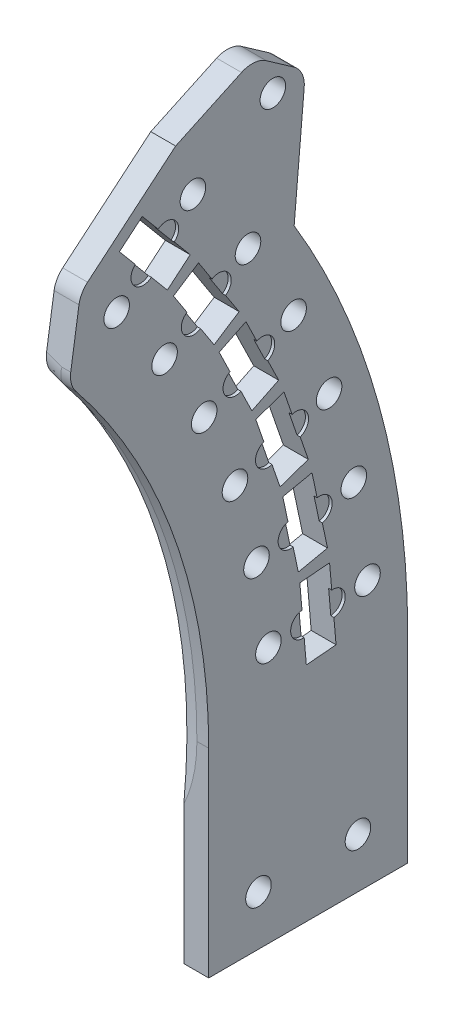
SolidWorks part; units mm, degrees
material "6061-T6 (SS)"
ref_plane "Front Plane" through (0, 0, 0) normal (0, 0, 1) x (1, 0, 0)
ref_plane "Top Plane" through (0, 0, 0) normal (0, 1, 0) x (1, 0, 0)
ref_plane "Right Plane" through (0, 0, 0) normal (1, 0, 0) x (0, 0, -1)
sketch "Sketch1" plane through (0, 0, 0) normal (1, 0, 0) x (0, 0, -1)
  line L0 (0, 0) -> (152.4, 0) construction
  line L1 (0, 0) -> (116.7452, 97.9608) construction
  line L2 (152.4, 0) -> (152.4, -50.8)
  line L3 (152.4, -50.8) -> (203.2, -50.8)
  line L4 (203.2, -50.8) -> (203.2, 0)
  line L5 (116.7452, 97.9608) -> (155.6602, 130.6144) construction
  line L6 (152.4, 0) -> (203.2, 0) construction
  line L7 (116.7452, 97.9608) -> (155.6602, 130.6144) construction
  line L9 (0, 0) -> (0, 168.3639) construction
  line L28 (152.4, -50.8) -> (152.4, -38.1) construction
  line L29 (152.4, -38.1) -> (203.2, -38.1) construction
  line L30 (0, 0) -> (136.2027, 114.2876) construction
  line L33 (155.6602, 130.6144) -> (143.9558, 137.372)
  line L34 (143.9558, 137.372) -> (119.6339, 116.9635)
  line L35 (119.6339, 116.9635) -> (116.7452, 97.9608)
  arc A0 (152.4, 0) -> (116.7452, 97.9608) centre (0, 0) ccw
  arc A1 (203.2, 0) -> (155.6602, 130.6144) centre (0, 0) ccw
  circle A32 centre (165.1, -38.1) radius 3.2639
  circle A33 centre (190.5, -38.1) radius 3.2639
  point P11 (151.8201, 13.2825)
  point P24 (150.0847, 26.464)
  dimension "D24" = 6.5278
  dimension "D25" = 6.5278
  dimension "D1" = 152.4
  dimension "D2" = 40
  dimension "D3" = 50.8
  dimension "D4" = 50.8
  dimension "D10" = 90
  dimension "D21" = 12.7
  dimension "D22" = 12.7
  dimension "D23" = 12.7
  dimension "D28" = 12.7
  dimension "D29" = 31.75
  dimension "D30" = 110
extrude "Boss-Extrude1" add sketch "Sketch1" along normal blind 6.35
sketch "Sketch2" plane through (0, 0, 0) normal (0, 1, 0) x (1, 0, 0)
  line L0 (0, 0) -> (-25.4, 0) construction
  line L1 (-25.4, 0) -> (-25.4, 38.1) construction
  line L2 (-25.4, 38.1) -> (-143.256, 38.1)
  line L3 (-143.256, 38.1) -> (92.456, 38.1)
  line L4 (0, 0) -> (-60.886, 0) construction
  arc A0 (92.456, 38.1) -> (-143.256, 38.1) centre (-25.4, 38.1) ccw
  dimension "D3" = 235.712
  dimension "D1" = 25.4
  dimension "D2" = 38.1
revolve "Cut-Revolve2" cut sketch "Sketch2" angle 360 about L4 region at (-25.4, 0, -88.1196)
sketch "Sketch5" plane through (0, 0, 0) normal (0, 0, 1) x (1, 0, 0)
  line L0 (-1000, 0) -> (49000, 0) construction
fillet "Fillet1" radius 6.35 4 edges at (4.8412, 97.9608, -116.7452) (3.175, 116.9635, -119.6339) (3.175, 130.6144, -155.6602)
sketch "Sketch6" plane through (6.35, 0, 0) normal (1, 0, 0) x (0, 0, -1)
  line L0 (0, 0) -> (177.8, 0) construction
  line L1 (0, 0) -> (136.2027, 114.2876) construction
  line L2 (0, 0) -> (192.938, 16.8799) construction
  line L3 (0, 0) -> (189.4427, 40.2673) construction
  line L4 (0, 0) -> (183.1233, 63.0544) construction
  line L5 (0, 0) -> (174.0739, 84.9015) construction
  line L6 (0, 0) -> (162.4295, 105.483) construction
  line L7 (0, 0) -> (148.3637, 124.4919) construction
  line L8 (0, 0) -> (167.6347, 14.6661) construction
  line L9 (0, 0) -> (164.5978, 34.9863) construction
  line L10 (175.6607, 24.9297) -> (177.321, 5.9522)
  line L11 (183.2517, 25.5938) -> (184.912, 6.6163)
  line L12 (175.6607, 24.9297) -> (183.2517, 25.5938)
  line L13 (184.912, 6.6163) -> (177.321, 5.9522)
  line L14 (182.7274, 29.1021) -> (175.2739, 27.5178)
  line L15 (171.3132, 46.1515) -> (175.2739, 27.5178)
  line L16 (171.3132, 46.1515) -> (178.7666, 47.7358)
  line L17 (178.7666, 47.7358) -> (182.7274, 29.1021)
  line L18 (177.8187, 51.154) -> (170.6138, 48.6732)
  line L19 (164.4118, 66.6853) -> (170.6138, 48.6732)
  line L20 (164.4118, 66.6853) -> (171.6166, 69.1662)
  line L21 (171.6166, 69.1662) -> (177.8187, 51.154)
  line L22 (170.2591, 72.4434) -> (163.4103, 69.103)
  line L23 (155.0594, 86.225) -> (163.4103, 69.103)
  line L24 (155.0594, 86.225) -> (161.9082, 89.5654)
  line L25 (161.9082, 89.5654) -> (170.2591, 72.4434)
  line L26 (160.1614, 92.6528) -> (153.7708, 88.5026)
  line L27 (143.3954, 104.4793) -> (153.7708, 88.5026)
  line L28 (143.3954, 104.4793) -> (149.7861, 108.6295)
  line L29 (149.7861, 108.6295) -> (160.1614, 92.6528)
  line L30 (147.6761, 111.4809) -> (141.8388, 106.5829)
  line L31 (129.5937, 121.176) -> (141.8388, 106.5829)
  line L32 (129.5937, 121.176) -> (135.431, 126.0741)
  line L33 (135.431, 126.0741) -> (147.6761, 111.4809)
  arc A0 (177.8, 0) -> (136.2027, 114.2876) centre (0, 0) ccw construction
  arc A1 (184.15, 0) -> (141.0671, 118.3693) centre (0, 0) ccw construction
  circle A2 centre (192.938, 16.8799) radius 9.525 construction
  arc A3 (203.2, 0) -> (156.395, 129.7338) centre (0, 0) ccw construction
  circle A4 centre (167.6347, 14.6661) radius 9.525 construction
  circle A5 centre (167.6347, 14.6661) radius 3.2639
  circle A6 centre (192.938, 16.8799) radius 3.2639
  circle A7 centre (164.5978, 34.9863) radius 3.2639
  circle A8 centre (164.5978, 34.9863) radius 9.525 construction
  circle A9 centre (189.4427, 40.2673) radius 3.2639
  circle A10 centre (189.4427, 40.2673) radius 9.525 construction
  circle A11 centre (159.1071, 54.785) radius 3.2639
  circle A12 centre (159.1071, 54.785) radius 9.525 construction
  circle A13 centre (183.1233, 63.0544) radius 3.2639
  circle A14 centre (183.1233, 63.0544) radius 9.525 construction
  circle A15 centre (151.2446, 73.7669) radius 3.2639
  circle A16 centre (151.2446, 73.7669) radius 9.525 construction
  circle A17 centre (174.0739, 84.9015) radius 3.2639
  circle A18 centre (174.0739, 84.9015) radius 9.525 construction
  circle A19 centre (141.1273, 91.6491) radius 3.2639
  circle A20 centre (141.1273, 91.6491) radius 9.525 construction
  circle A21 centre (162.4295, 105.483) radius 3.2639
  circle A22 centre (162.4295, 105.483) radius 9.525 construction
  circle A23 centre (128.9061, 108.1651) radius 3.2639
  circle A24 centre (128.9061, 108.1651) radius 9.525 construction
  circle A25 centre (148.3637, 124.4919) radius 3.2639
  circle A26 centre (148.3637, 124.4919) radius 9.525 construction
  dimension "D3" = 19.05
  dimension "D4" = 19.05
  dimension "D6" = 6.5278
  dimension "D7" = 6.5278
  dimension "D13" = 8.89
  dimension "D2" = 40
  dimension "D5" = 5
  dimension "D9" = 7
  dimension "D10" = 19.05
  dimension "D11" = 9.525
  dimension "D1" = 6.35
  dimension "D12" = 7.62
  dimension "D8" = 6
extrude "Cut-Extrude1" cut sketch "Sketch6" against normal through all
sketch "Sketch8" plane through (6.35, 15.5516, -177.756) normal (1, 0, 0) x (0, 0.0872, -0.9962)
  line L0 (6.35, 0) -> (8.7312, 0) construction
  line L1 (6.35, -9.525) -> (6.35, 9.525) construction
  line L2 (6.35, 3.175) -> (-1.27, 3.175)
  line L3 (-1.27, 9.525) -> (-1.27, -9.525) construction
  line L4 (-1.27, -3.175) -> (6.35, -3.175)
  arc A1 (6.35, 3.175) -> (6.35, -3.175) centre (6.35, 0) cw
  arc A2 (-1.27, 3.175) -> (-1.27, -3.175) centre (-1.27, 0) ccw
  dimension "D1" = 3.175
  dimension "D2" = 2.3812
extrude "Cut-Extrude2" cut sketch "Sketch8" against normal blind 0.7937 and the other way blind 10.033
pattern_circular "CirPattern1" count 6 every 7 about axis through (6.35, 0, 0) along (-1, 0, 0) of "Cut-Extrude2" reverse direction yes
sketch "Sketch9" plane through (6.35, 0, 0) normal (1, 0, 0) x (0, 0, -1)
  line L0 (0, 0) -> (168.7728, 136.6695) construction
  line L1 (0, 0) -> (72.4364, 0) construction
  circle A0 centre (168.7728, 136.6695) radius 3.2639
  dimension "D3" = 6.5278
  dimension "D1" = 217.17
  dimension "D2" = 39
sketch "Sketch11" plane through (6.35, 0, 0) normal (1, 0, 0) x (0, 0, -1)
  line L0 (143.9558, 137.372) -> (164.0985, 146.7647)
  line L1 (164.0985, 146.7647) -> (177.1026, 137.6591)
  line L2 (177.1026, 137.6591) -> (174.2102, 104.5994)
  line L3 (143.9558, 137.372) -> (121.4699, 118.504) construction
  line L10 (119.2737, 114.594) -> (117.1712, 100.7636)
  line L11 (152.4, 0) -> (152.4, -50.8)
  line L12 (152.4, -50.8) -> (203.2, -50.8)
  line L13 (203.2, -50.8) -> (203.2, 0)
  line L14 (154.6826, 131.1789) -> (143.9558, 137.372)
  line L15 (143.9558, 137.372) -> (121.4699, 118.504)
  line L16 (119.2737, 114.594) -> (117.1712, 100.7636)
  line L17 (152.4, 0) -> (152.4, -50.8)
  line L18 (152.4, -50.8) -> (203.2, -50.8)
  line L19 (203.2, -50.8) -> (203.2, 0)
  line L20 (154.6826, 131.1789) -> (143.9558, 137.372)
  line L21 (143.9558, 137.372) -> (121.4699, 118.504)
  arc A0 (203.2, 0) -> (156.395, 129.7338) centre (0, 0) ccw construction
  arc A6 (117.1712, 100.7636) -> (118.5112, 95.8168) centre (123.4491, 99.8092) ccw
  arc A7 (152.4, 0) -> (118.5112, 95.8168) centre (0, 0) ccw
  arc A8 (203.2, 0) -> (156.395, 129.7338) centre (0, 0) ccw
  arc A9 (156.395, 129.7338) -> (154.6826, 131.1789) centre (151.5076, 125.6796) ccw
  arc A10 (121.4699, 118.504) -> (119.2737, 114.594) centre (125.5516, 113.6396) ccw
  arc A11 (117.1712, 100.7636) -> (118.5112, 95.8168) centre (123.4491, 99.8092) ccw
  arc A12 (152.4, 0) -> (118.5112, 95.8168) centre (0, 0) ccw
  arc A13 (203.2, 0) -> (156.395, 129.7338) centre (0, 0) ccw
  arc A14 (156.395, 129.7338) -> (154.6826, 131.1789) centre (151.5076, 125.6796) ccw
  arc A15 (121.4699, 118.504) -> (119.2737, 114.594) centre (125.5516, 113.6396) ccw
  dimension "D1" = 165
  dimension "D2" = 22.225
  dimension "D3" = 15.875
  dimension "D4" = 120
  dimension "D5" = 120
  dimension "D6" = 0
extrude "Boss-Extrude2" add sketch "Sketch11" against normal blind 6.35 contours A14 A13 L2 L1 L0 L20 region at (6.35, 130.6878, -165.2969)
extrude "Cut-Extrude3" cut sketch "Sketch9" against normal through all both and the other way through all
fillet "Fillet2" radius 6.35 2 edges at (3.175, 137.6591, -177.1026) (3.175, 146.7647, -164.0985)
